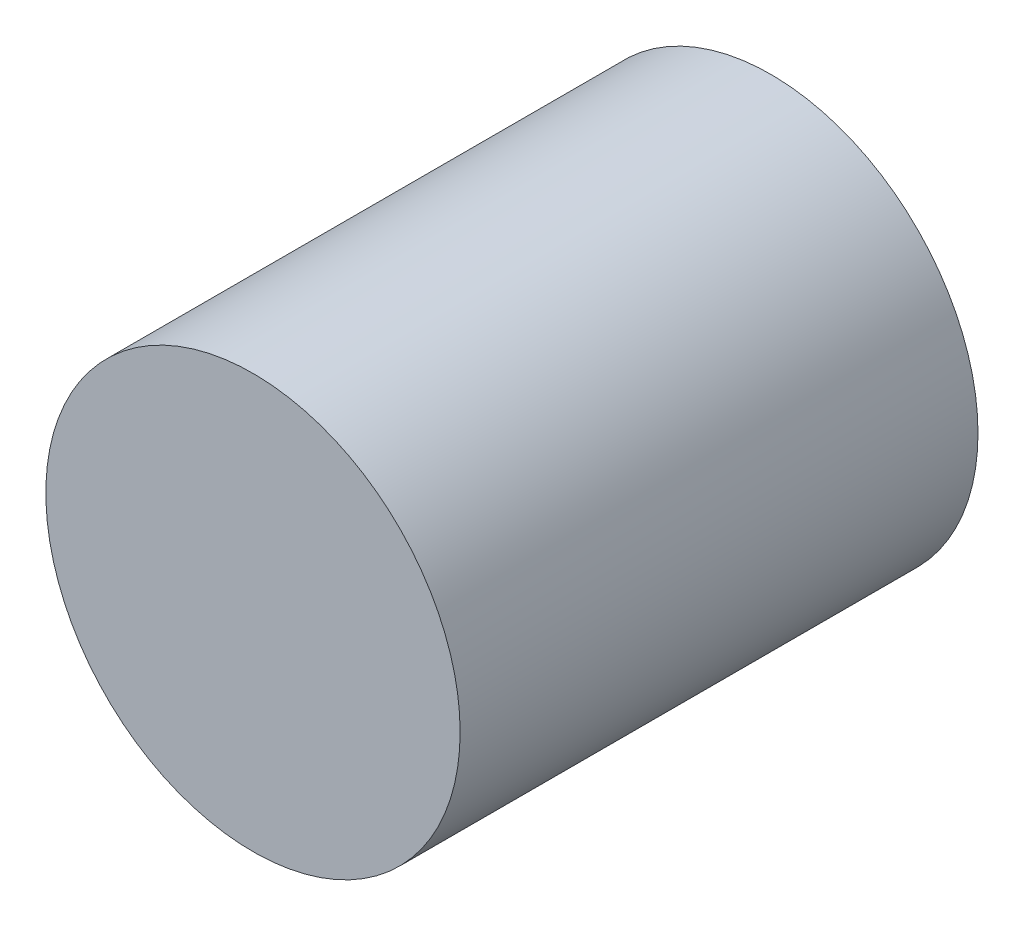
SolidWorks part; units mm, degrees
ref_plane "前视基准面" through (0, 0, 0) normal (0, 0, 1) x (1, 0, 0)
ref_plane "上视基准面" through (0, 0, 0) normal (0, 1, 0) x (1, 0, 0)
ref_plane "右视基准面" through (0, 0, 0) normal (1, 0, 0) x (0, 0, -1)
sketch "草图1" plane through (0, 0, 0) normal (0, 0, 1) x (1, 0, 0)
  circle A0 centre (0, 0) radius 20
extrude "凸台-拉伸1" add sketch "草图1" along normal blind 50
ref_point "点2"
ref_point "点4"
sketch "草图2" plane through (0, 0, 50) normal (0, 0, 1) x (1, 0, 0)
  line L0 (0, 0) -> (0, 20)
  circle A0 centre (0, 0) radius 20 construction
sketch "草图3" plane through (0, 0, 0) normal (0, 0, -1) x (-1, 0, 0)
  line L0 (0, 0) -> (0, 20)
ref_axis "基准轴1" through (0, 0, 0) along (0, 0, -1)
ref_axis "基准轴2" through (0, 0, 50) along (0, 0, 1)
ref_axis "基准轴3" through (0, 0, 50) along (0, 1, 0)
ref_axis "基准轴4" through (0, 0, 0) along (0, 1, 0)
